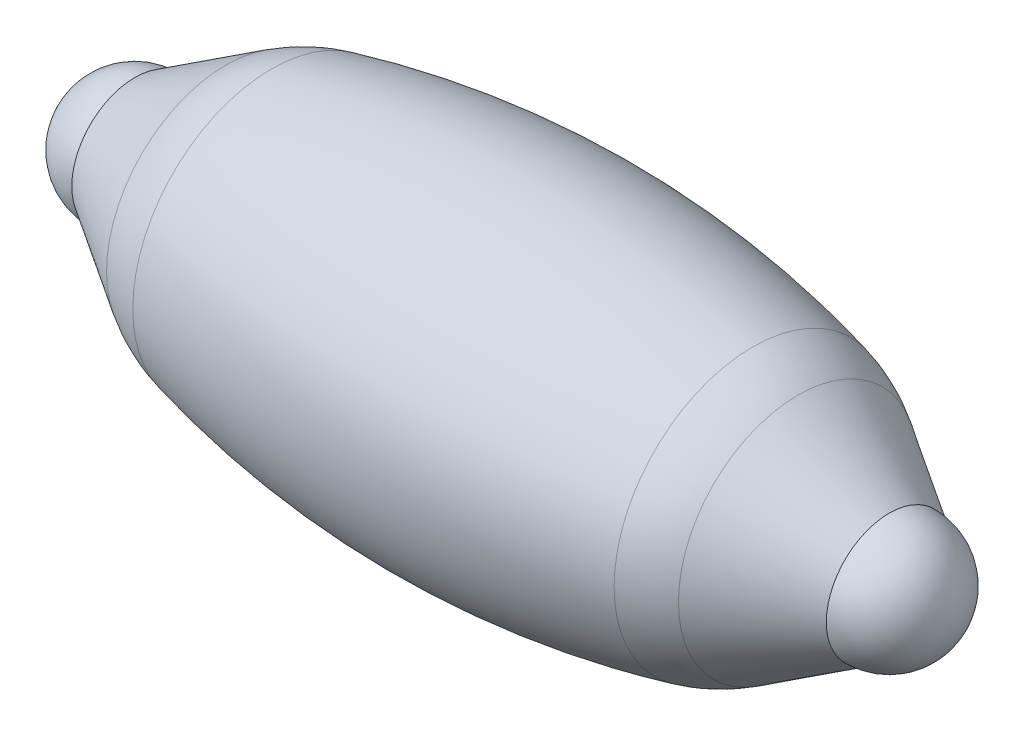
SolidWorks part; units mm, degrees
ref_plane "Ebene vorne" through (0, 0, 0) normal (0, 0, 1) x (1, 0, 0)
ref_plane "Ebene oben" through (0, 0, 0) normal (0, 1, 0) x (1, 0, 0)
ref_plane "Ebene rechts" through (0, 0, 0) normal (1, 0, 0) x (0, 0, -1)
sketch "Skizze2" plane through (0, 0, 0) normal (0, 0, 1) x (1, 0, 0)
  line L0 (0, 0) -> (0, 56.995) construction
  line L1 (0, 0) -> (-11.9874, 29.6699) construction
  line L2 (0, 0) -> (11.9874, 29.6699) construction
  line L3 (-11.9874, 29.6699) -> (-11.9874, 26.6699)
  line L4 (11.9874, 29.6699) -> (11.9874, 26.6699)
  line L5 (-11.9874, 26.6699) -> (11.9874, 26.6699)
  arc A0 (-11.9874, 29.6699) -> (11.9874, 29.6699) centre (0, 0) cw
  dimension "D1" = 44
  dimension "D3" = 32
  dimension "D5" = 3
  dimension "D2" = 22
  dimension "D4" = 32
  dimension "D6" = 3
revolve "Rotation1" add sketch "Skizze2" angle 360 about L5
sketch "Skizze3" plane through (-11.9874, 0, 0) normal (-1, 0, 0) x (0, 0, 1)
  line L0 (0, 29.6699) -> (0, 23.6699) construction
  circle A0 centre (0, 26.6699) radius 3 construction
chamfer "Fase1" distance 5 distance2 1 1 edges at (-11.9874, 23.6699, 0) first distance on face at (-11.9874, 23.6699, 0)
chamfer "Fase2" distance 1 distance2 5 1 edges at (11.9874, 23.6699, 0) first distance on face at (11.9874, 23.6699, 0)
sketch "Skizze4" plane through (-11.9874, 0, 0) normal (-1, 0, 0) x (0, 0, 1)
  line L0 (0, 29.6699) -> (0, 23.6699) construction
  circle A0 centre (0, 26.6699) radius 2
extrude "Aufsatz-Linear austragen2" add sketch "Skizze4" along normal blind 2
fillet "Verrundung6" radius 2 1 edges at (-13.9874, 24.6699, 0)
sketch "Skizze5" plane through (11.9874, 0, 0) normal (1, 0, 0) x (0, 0, -1)
  line L0 (0, 29.6699) -> (0, 23.6699) construction
  circle A0 centre (0, 26.6699) radius 2
extrude "Aufsatz-Linear austragen3" add sketch "Skizze5" along normal blind 2
fillet "Verrundung7" radius 2 1 edges at (13.9874, 28.6699, 0)
fillet "Verrundung8" radius 5 2 edges at (8.4441, 26.6699, 4.1959) (-8.4441, 30.8658, 0)
